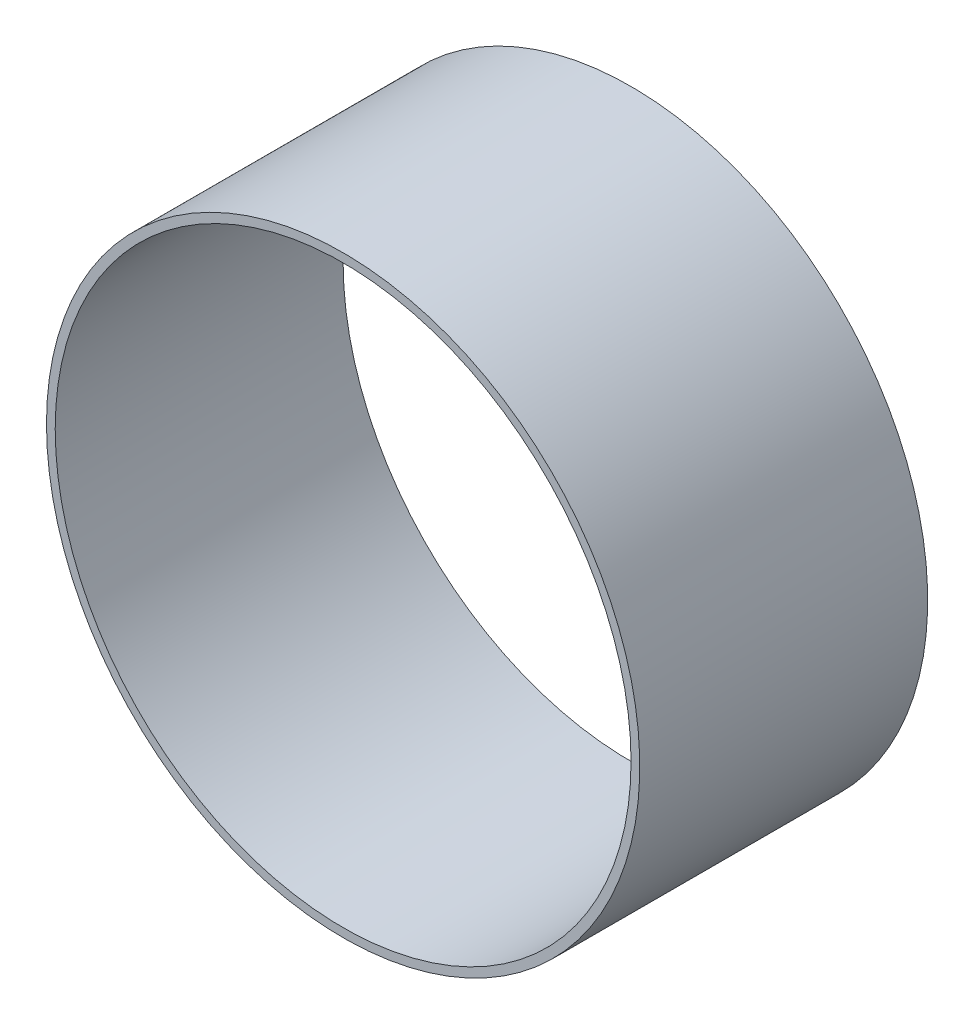
SolidWorks part; units mm, degrees
ref_plane "Front Plane" through (0, 0, 0) normal (0, 0, 1) x (1, 0, 0)
ref_plane "Top Plane" through (0, 0, 0) normal (0, 1, 0) x (1, 0, 0)
ref_plane "Right Plane" through (0, 0, 0) normal (1, 0, 0) x (0, 0, -1)
sketch "Sketch1" plane through (0, 0, 0) normal (0, 0, 1) x (1, 0, 0)
  circle A0 centre (0, 0) radius 39.2557
  circle A1 centre (0, 0) radius 38.1
  dimension "D1" = 76.2
  dimension "D2" = 78.5114
extrude "Boss-Extrude1" add sketch "Sketch1" along normal mid plane 38.1
equation "\"AIRFRAME_OD\"= 3.091in"
equation "\"AIRFRAME_ID\"= 3.00in"
equation "\"FLAT_T\" = 0.125in"
equation "\"NOSE_EXP_L\"= 3.5in"
equation "\"NOSE_SHOULDER_L\" = 5in"
equation "\"MAIN_L\" = 30in"
equation "\"RECO_COUP_L\" = 6in"
equation "\"RECO_SWITCH_L\" = 1.5in"
equation "\"DROGUE_L\" = 14in"
equation "\"ATS_FORE_COUP_L\" = 4in"
equation "\"ATS_AFT_COUP_L\" = 4in"
equation "\"LOWER_L\" = 16in"
equation "\"FIN_N\" = 4"
equation "\"CR_AFT_X\" = 0.5in"
equation "\"CR_FORE_X\" = 6in"
equation "\"D1@Sketch1\"=\"AIRFRAME_ID\""
equation "\"D2@Sketch1\"=\"AIRFRAME_OD\""
equation "\"D1@Boss-Extrude1\"=\"RECO_SWITCH_L\""
equation "\"FIN_ROOT\" = 5in"
equation "\"FIN_X\" = 0.75in"
equation "\"MOTOR_OD\" = 2.25in"
equation "\"MOTOR_ID\" = 2.126in"
